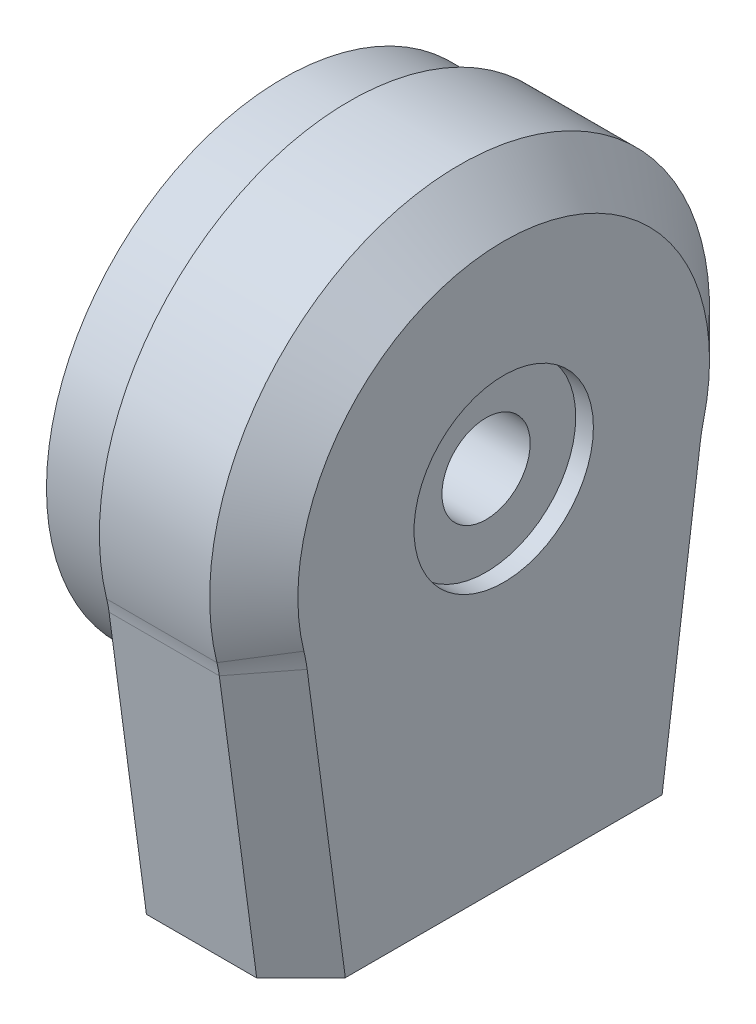
SolidWorks part; units mm, degrees
ref_plane "Front Plane" through (0, 0, 0) normal (0, 0, 1) x (1, 0, 0)
ref_plane "Top Plane" through (0, 0, 0) normal (0, 1, 0) x (1, 0, 0)
ref_plane "Right Plane" through (0, 0, 0) normal (1, 0, 0) x (0, 0, -1)
sketch "Sketch1" plane through (0, 0, 0) normal (1, 0, 0) x (0, 0, -1)
  line L0 (-49.6573, -24.9297) -> (-54.0465, -57.8487)
  line L1 (-52.95, -60.6) -> (-52.95, -69.4)
  line L2 (-56.95, -73.4) -> (-85.85, -73.4)
  line L3 (-89.85, -69.4) -> (-89.85, -60.6)
  line L4 (-85.85, -56.6) -> (-78.12, -56.6)
  line L5 (-78.12, -56.6) -> (-82.3427, -24.9297)
  arc A0 (-82.5053, -24.0712) -> (-49.4947, -24.0712) centre (-66, -20) cw
  arc A1 (-49.4947, -24.0712) -> (-49.6573, -24.9297) centre (-41.7275, -25.987) ccw
  arc A2 (-54.0465, -57.8487) -> (-52.95, -60.6) centre (-56.95, -60.6) cw
  arc A3 (-52.95, -69.4) -> (-56.95, -73.4) centre (-56.95, -69.4) cw
  arc A4 (-85.85, -73.4) -> (-89.85, -69.4) centre (-85.85, -69.4) cw
  arc A5 (-89.85, -60.6) -> (-85.85, -56.6) centre (-85.85, -60.6) cw
  arc A6 (-82.3427, -24.9297) -> (-82.5053, -24.0712) centre (-90.2725, -25.987) ccw
extrude "Boss-Extrude1" add sketch "Sketch1" along normal blind 10.5 from offset 65.9
sketch "Sketch2" plane through (0, 0, 0) normal (1, 0, 0) x (0, 0, -1)
  line L0 (-50.4503, -24.824) -> (-54.8935, -58.1483)
  line L1 (-53.75, -60.6) -> (-53.75, -69.4)
  line L2 (-56.95, -72.6) -> (-85.85, -72.6)
  line L3 (-89.05, -69.4) -> (-89.05, -60.6)
  line L4 (-85.85, -57.4) -> (-77.2063, -57.4)
  line L5 (-77.2063, -57.4) -> (-81.5497, -24.824)
  arc A0 (-81.7286, -23.8796) -> (-50.2714, -23.8796) centre (-66, -20) cw
  arc A1 (-50.2714, -23.8796) -> (-50.4503, -24.824) centre (-41.7275, -25.987) ccw
  arc A2 (-54.8935, -58.1483) -> (-53.75, -60.6) centre (-56.95, -60.6) cw
  arc A3 (-53.75, -69.4) -> (-56.95, -72.6) centre (-56.95, -69.4) cw
  arc A4 (-85.85, -72.6) -> (-89.05, -69.4) centre (-85.85, -69.4) cw
  arc A5 (-89.05, -60.6) -> (-85.85, -57.4) centre (-85.85, -60.6) cw
  arc A6 (-81.5497, -24.824) -> (-81.7286, -23.8796) centre (-90.2725, -25.987) ccw
extrude "Boss-Extrude2" add sketch "Sketch2" along normal blind 0.6 from offset 65.8 separate body
combine bodies "Combine1" operation type subtract main body 101 bodies to subtract 102
chamfer "Chamfer1" distance 3 angle 45 5 edges at (76.4, -41.3892, 51.8519) (76.4, -40.7649, 80.2314) (76.4, -24.4982, 49.5877) (76.4, -24.4982, 82.4123) (76.4, -3, 66)
chamfer "Chamfer2" distance 3 angle 45 8 edges at (76.4, -56.6, 80.4717) (76.4, -57.7716, 88.6784) (76.4, -57.787, 54.1063) (76.4, -65, 89.85) (76.4, -65, 52.95) (76.4, -72.2284, 88.6784) (76.4, -72.2284, 54.1216) (76.4, -73.4, 71.4)
sketch "Sketch3" plane through (0, 0, 0) normal (0, 0, 1) x (1, 0, 0)
  line L1 (65.9, -31.5) -> (68.2, -31.5)
  line L2 (65.9, -31.5) -> (65.9, -8.5)
  line L3 (65.9, -8.5) -> (68.2, -8.5)
  line L4 (68.2, -31.5) -> (68.2, -8.5)
extrude "Boss-Extrude3" add sketch "Sketch3" along normal blind 6.6 from offset 62.7 separate body
combine bodies "Combine2" operation type subtract main body 103 bodies to subtract 104
sketch "Sketch4" plane through (0, 0, 0) normal (0, 0, 1) x (1, 0, 0)
  line L1 (65.9, -23.3) -> (68.2, -23.3)
  line L2 (65.9, -23.3) -> (65.9, -16.7)
  line L3 (65.9, -16.7) -> (68.2, -16.7)
  line L4 (68.2, -23.3) -> (68.2, -16.7)
extrude "Boss-Extrude4" add sketch "Sketch4" along normal blind 23 from offset 54.5 separate body
combine bodies "Combine3" operation type subtract main body 105 bodies to subtract 106
sketch "Sketch5" plane through (0, 0, 0) normal (1, 0, 0) x (0, 0, -1)
  circle A0 centre (-66, -20) radius 4.6
extrude "Boss-Extrude5" add sketch "Sketch5" along normal blind 2.3 from offset 65.9 separate body
combine bodies "Combine4" operation type subtract main body 107 bodies to subtract 108
sketch "Sketch6" plane through (0, 0, 0) normal (1, 0, 0) x (0, 0, -1)
  circle A0 centre (-66, -20) radius 6.1
extrude "Boss-Extrude6" add sketch "Sketch6" along normal blind 1.7 from offset 75.2 separate body
combine bodies "Combine5" operation type subtract main body 109 bodies to subtract 110
sketch "Sketch7" plane through (0, 0, 0) normal (1, 0, 0) x (0, 0, -1)
  circle A0 centre (-66, -20) radius 3
extrude "Boss-Extrude7" add sketch "Sketch7" along normal blind 7.2 from offset 68.1 separate body
combine bodies "Combine6" operation type subtract main body 111 bodies to subtract 112
sketch "Sketch8" plane through (0, 0, 0) normal (0, 0, 1) x (1, 0, 0)
  line L1 (68.1, -14.5) -> (74.2, -14.5)
  line L2 (68.1, -14.5) -> (68.1, -13.4)
  line L3 (68.1, -13.4) -> (74.2, -13.4)
  line L4 (74.2, -14.5) -> (74.2, -13.4)
extrude "Boss-Extrude8" add sketch "Sketch8" along normal blind 1.8 from offset 65.1 separate body
combine bodies "Combine7" operation type subtract main body 113 bodies to subtract 114
sketch "Sketch9" plane through (0, 0, 0) normal (0, 0, 1) x (1, 0, 0)
  line L1 (68.1, -20.9) -> (74.2, -20.9)
  line L2 (68.1, -20.9) -> (68.1, -19.1)
  line L3 (68.1, -19.1) -> (74.2, -19.1)
  line L4 (74.2, -20.9) -> (74.2, -19.1)
extrude "Boss-Extrude9" add sketch "Sketch9" along normal blind 1.1 from offset 71.5 separate body
combine bodies "Combine8" operation type subtract main body 115 bodies to subtract 116
sketch "Sketch10" plane through (0, 0, 0) normal (0, 0, 1) x (1, 0, 0)
  line L1 (68.1, -26.6) -> (74.2, -26.6)
  line L2 (68.1, -26.6) -> (68.1, -25.5)
  line L3 (68.1, -25.5) -> (74.2, -25.5)
  line L4 (74.2, -26.6) -> (74.2, -25.5)
extrude "Boss-Extrude10" add sketch "Sketch10" along normal blind 1.8 from offset 65.1 separate body
combine bodies "Combine9" operation type subtract main body 117 bodies to subtract 118
sketch "Sketch11" plane through (0, 0, 0) normal (0, 0, 1) x (1, 0, 0)
  line L1 (68.1, -20.9) -> (74.2, -20.9)
  line L2 (68.1, -20.9) -> (68.1, -19.1)
  line L3 (68.1, -19.1) -> (74.2, -19.1)
  line L4 (74.2, -20.9) -> (74.2, -19.1)
extrude "Boss-Extrude11" add sketch "Sketch11" along normal blind 1.1 from offset 59.4 separate body
combine bodies "Combine10" operation type subtract main body 119 bodies to subtract 120
sketch "Sketch12" plane through (0, 0, 0) normal (0, 0, 1) x (1, 0, 0)
  line L1 (68.1, -13.4) -> (75.4, -13.4)
  line L2 (68.1, -13.4) -> (68.1, -10)
  line L3 (68.1, -10) -> (75.4, -10)
  line L4 (75.4, -13.4) -> (75.4, -10)
extrude "Boss-Extrude12" add sketch "Sketch12" along normal blind 1.8 from offset 65.1 separate body
combine bodies "Combine11" operation type subtract main body 121 bodies to subtract 122
sketch "Sketch13" plane through (0, 0, 0) normal (0, 0, 1) x (1, 0, 0)
  line L1 (68.1, -20.9) -> (75.4, -20.9)
  line L2 (68.1, -20.9) -> (68.1, -19.1)
  line L3 (68.1, -19.1) -> (75.4, -19.1)
  line L4 (75.4, -20.9) -> (75.4, -19.1)
extrude "Boss-Extrude13" add sketch "Sketch13" along normal blind 3.4 from offset 72.6 separate body
combine bodies "Combine12" operation type subtract main body 123 bodies to subtract 124
sketch "Sketch14" plane through (0, 0, 0) normal (0, 0, 1) x (1, 0, 0)
  line L1 (68.1, -30) -> (75.4, -30)
  line L2 (68.1, -30) -> (68.1, -26.6)
  line L3 (68.1, -26.6) -> (75.4, -26.6)
  line L4 (75.4, -30) -> (75.4, -26.6)
extrude "Boss-Extrude14" add sketch "Sketch14" along normal blind 1.8 from offset 65.1 separate body
combine bodies "Combine13" operation type subtract main body 125 bodies to subtract 126
sketch "Sketch15" plane through (0, 0, 0) normal (0, 0, 1) x (1, 0, 0)
  line L1 (68.1, -20.9) -> (75.4, -20.9)
  line L2 (68.1, -20.9) -> (68.1, -19.1)
  line L3 (68.1, -19.1) -> (75.4, -19.1)
  line L4 (75.4, -20.9) -> (75.4, -19.1)
extrude "Boss-Extrude15" add sketch "Sketch15" along normal blind 3.4 from offset 56 separate body
combine bodies "Combine14" operation type subtract main body 127 bodies to subtract 128
sketch "Sketch16" plane through (0, 0, 0) normal (1, 0, 0) x (0, 0, -1)
  line L0 (-51.9046, -14.8697) -> (-52.4684, -15.0749)
  line L1 (-79.5316, -15.0749) -> (-80.0954, -14.8697)
  arc A0 (-80.0954, -14.8697) -> (-51.9046, -14.8697) centre (-66, -20) cw
  arc A1 (-52.4684, -15.0749) -> (-79.5316, -15.0749) centre (-66, -20) ccw
extrude "Boss-Extrude16" add sketch "Sketch16" along normal blind 2.05 from offset 64.4
sketch "Sketch17" plane through (0, 0, 0) normal (1, 0, 0) x (0, 0, -1)
  circle A0 centre (-66, -20) radius 16.1
  circle A1 centre (-66, -20) radius 15.2
extrude "Boss-Extrude17" add sketch "Sketch17" along normal blind 5.05 from offset 61.4
sketch "Sketch18" plane through (0, 0, 0) normal (0, 0, 1) x (1, 0, 0)
  line L1 (63.2, -38) -> (66.4, -38)
  line L2 (63.2, -38) -> (63.2, -34)
  line L3 (63.2, -34) -> (66.4, -34)
  line L4 (66.4, -38) -> (66.4, -34)
extrude "Boss-Extrude18" add sketch "Sketch18" along normal blind 6 from offset 63 separate body
combine bodies "Combine15" operation type subtract main body 131 bodies to subtract 132
sketch "Sketch19" plane through (0, 0, 0) normal (0, 0, 1) x (1, 0, 0)
  line L1 (60, -100) -> (80, -100)
  line L2 (60, -100) -> (60, -44)
  line L3 (60, -44) -> (80, -44)
  line L4 (80, -100) -> (80, -44)
extrude "Boss-Extrude19" add sketch "Sketch19" along normal blind 80 from offset 26 separate body
combine bodies "Combine16" operation type subtract main body 133 bodies to subtract 134
